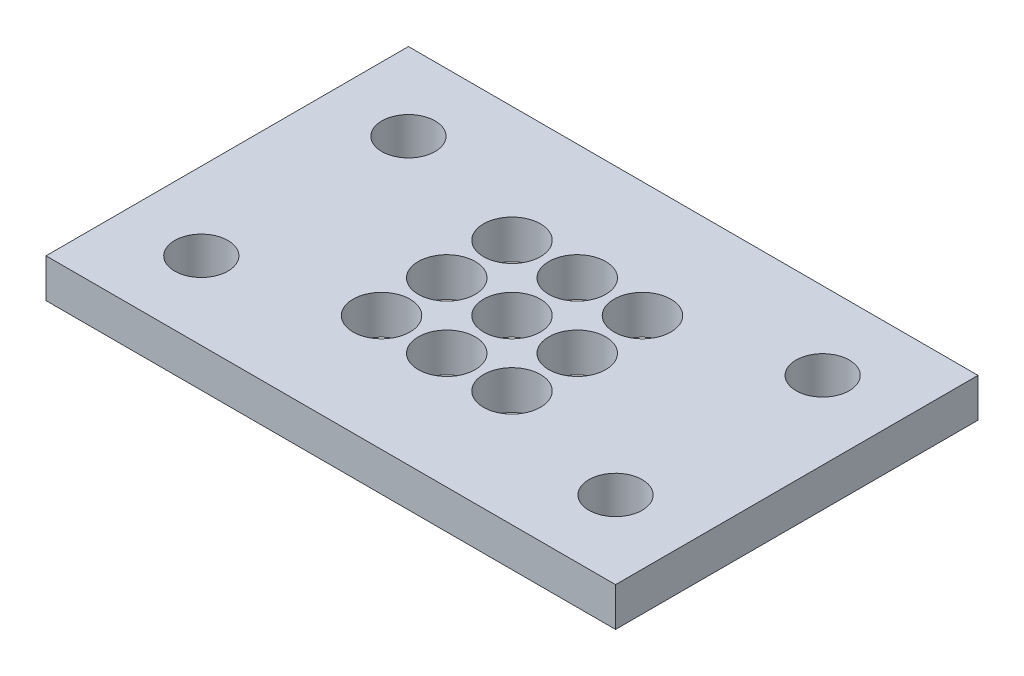
SolidWorks part; units mm, degrees
ref_plane "Front Plane" through (0, 0, 0) normal (0, 0, 1) x (1, 0, 0)
ref_plane "Top Plane" through (0, 0, 0) normal (0, 1, 0) x (1, 0, 0)
ref_plane "Right Plane" through (0, 0, 0) normal (1, 0, 0) x (0, 0, -1)
sketch "Sketch1" plane through (0, 0, 0) normal (0, 1, 0) x (1, 0, 0)
  line L0 (9.525, 34.925) -> (0, 34.925) construction
  line L1 (0, 0) -> (69.85, 0)
  line L2 (0, 0) -> (0, 44.45)
  line L3 (0, 44.45) -> (69.85, 44.45)
  line L4 (69.85, 0) -> (69.85, 44.45)
  line L5 (9.525, 34.925) -> (60.325, 34.925) construction
  line L6 (9.525, 34.925) -> (9.525, 9.525) construction
  line L7 (9.525, 9.525) -> (60.325, 9.525) construction
  line L8 (60.325, 34.925) -> (60.325, 9.525) construction
  line L9 (9.525, 34.925) -> (9.525, 44.45) construction
  circle A0 centre (9.525, 34.925) radius 3.2639
  circle A1 centre (60.325, 34.925) radius 3.2639
  circle A2 centre (9.525, 9.525) radius 3.2639
  circle A3 centre (60.325, 9.525) radius 3.2639
  circle A4 centre (34.925, 22.225) radius 3.4925
  circle A5 centre (42.925, 22.225) radius 3.4925
  circle A6 centre (42.925, 30.225) radius 3.4925
  circle A7 centre (34.925, 30.225) radius 3.4925
  circle A8 centre (26.925, 22.225) radius 3.4925
  circle A9 centre (26.925, 30.225) radius 3.4925
  circle A10 centre (34.925, 30.225) radius 3.4925
  circle A11 centre (26.925, 22.225) radius 3.4925
  circle A12 centre (26.925, 14.225) radius 3.4925
  circle A13 centre (34.925, 14.225) radius 3.4925
  circle A14 centre (42.925, 22.225) radius 3.4925
  circle A15 centre (42.925, 14.225) radius 3.4925
  circle A16 centre (34.925, 14.225) radius 3.4925
  point P13 (34.925, 34.925)
  point P14 (34.925, 44.45)
  point P20 (69.85, 22.225)
  dimension "D5" = 6.5278
  dimension "D6" = 6.985
  dimension "D1" = 69.85
  dimension "D2" = 44.45
  dimension "D3" = 50.8
  dimension "D4" = 25.4
  dimension "D7" = 2
  dimension "D8" = 2
  dimension "D9" = 2
  dimension "D10" = 2
  dimension "D11" = 2
  dimension "D12" = 2
  dimension "D13" = 2
  dimension "D14" = 2
extrude "Boss-Extrude1" add sketch "Sketch1" along normal blind 4.7625 contours L1 L4 L3 L2 A15 A13 A12 A9 A8 A7 A6 A5 A4 A3 A2 A1 A0 region at (0.8279, 0, -22.225)
